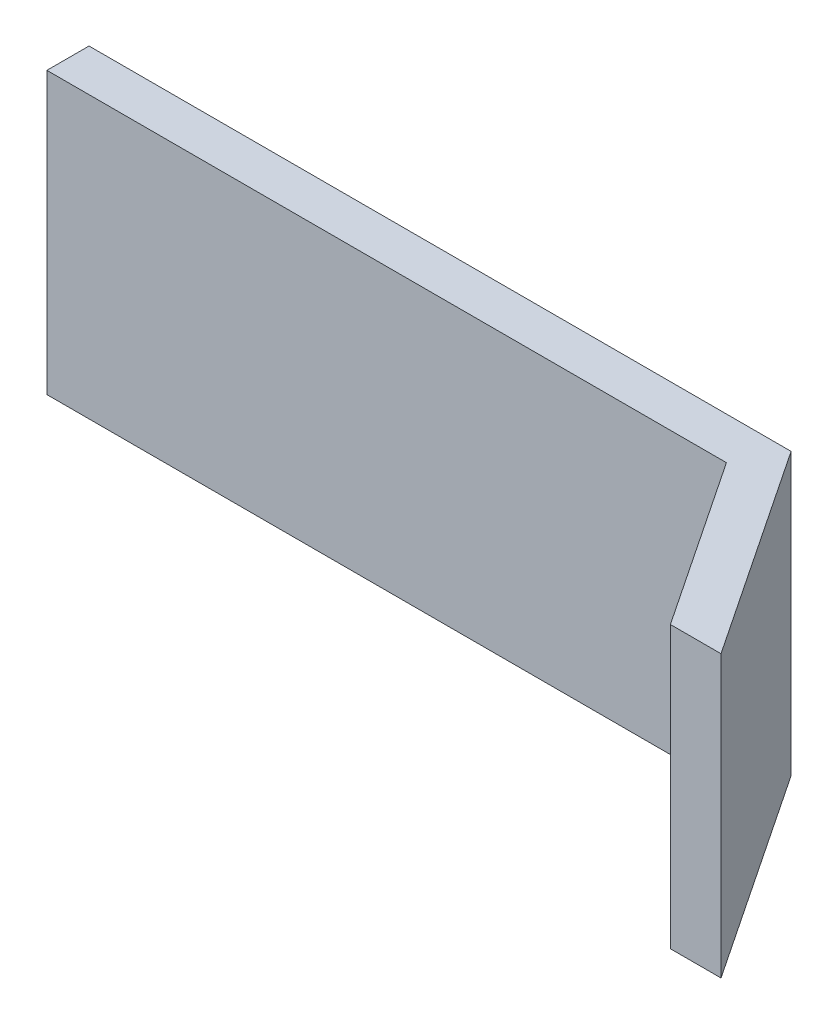
SolidWorks part; units mm, degrees
ref_plane "Front Plane" through (0, 0, 0) normal (0, 0, 1) x (1, 0, 0)
ref_plane "Top Plane" through (0, 0, 0) normal (0, 1, 0) x (1, 0, 0)
ref_plane "Right Plane" through (0, 0, 0) normal (1, 0, 0) x (0, 0, -1)
sketch "Sketch1" plane through (0, 0, 0) normal (0, 1, 0) x (1, 0, 0)
  line L0 (0, 0) -> (0, 3)
  line L1 (0, 3) -> (50, 3)
  line L2 (50, 3) -> (59.9846, -11.9769)
  line L3 (0, 0) -> (48.3944, 0)
  line L4 (48.3944, 0) -> (56.379, -11.9769)
  line L5 (56.379, -11.9769) -> (59.9846, -11.9769)
  dimension "D1" = 3
  dimension "D2" = 3
  dimension "D3" = 56.31
  dimension "D4" = 18
  dimension "D5" = 50
extrude "Boss-Extrude1" add sketch "Sketch1" along normal blind 20
